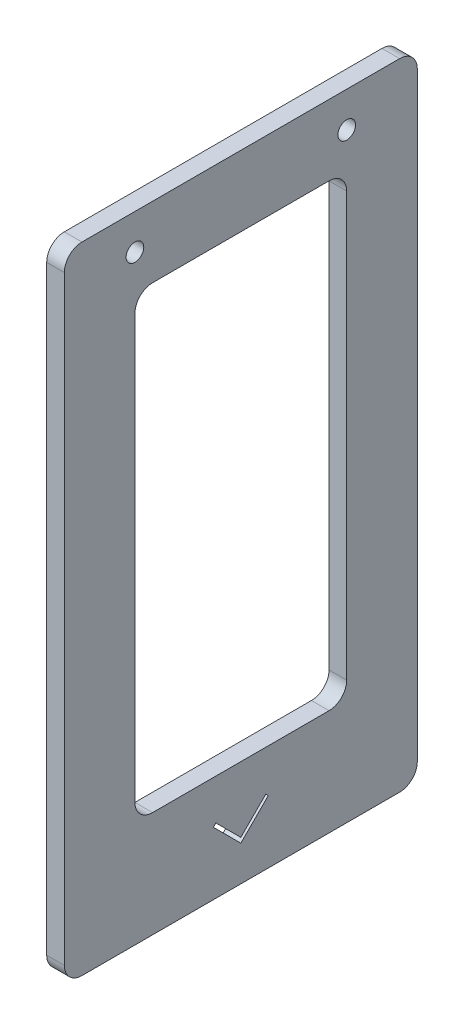
SolidWorks part; units mm, degrees
material "Balsa"
ref_plane "Front Plane" through (0, 0, 0) normal (0, 0, 1) x (1, 0, 0)
ref_plane "Top Plane" through (0, 0, 0) normal (0, 1, 0) x (1, 0, 0)
ref_plane "Right Plane" through (0, 0, 0) normal (1, 0, 0) x (0, 0, -1)
sketch "Sketch3" plane through (0, 0, 0) normal (1, 0, 0) x (0, 0, -1)
  line L0 (-31.75, -76.2) -> (31.75, -76.2)
  line L1 (-57.15, -114.3) -> (57.15, -114.3)
  line L2 (-63.5, -107.95) -> (-63.5, 107.95)
  line L3 (-57.15, 114.3) -> (57.15, 114.3)
  line L4 (63.5, -107.95) -> (63.5, 107.95)
  line L5 (-63.5, -114.3) -> (63.5, 114.3) construction
  line L6 (-63.5, 114.3) -> (63.5, -114.3) construction
  line L8 (-38.1, -69.85) -> (-38.1, 82.55)
  line L9 (-31.75, 88.9) -> (31.75, 88.9)
  line L11 (0, 0) -> (38.1, 88.9) construction
  line L12 (-38.1, 88.9) -> (0, 0) construction
  line L13 (38.1, -69.85) -> (38.1, 82.55)
  arc A0 (-57.15, -114.3) -> (-63.5, -107.95) centre (-57.15, -107.95) cw
  arc A1 (63.5, -107.95) -> (57.15, -114.3) centre (57.15, -107.95) cw
  arc A2 (63.5, 107.95) -> (57.15, 114.3) centre (57.15, 107.95) ccw
  arc A3 (-63.5, 107.95) -> (-57.15, 114.3) centre (-57.15, 107.95) cw
  arc A4 (31.75, -76.2) -> (38.1, -69.85) centre (31.75, -69.85) ccw
  arc A5 (-31.75, -76.2) -> (-38.1, -69.85) centre (-31.75, -69.85) cw
  arc A6 (31.75, 88.9) -> (38.1, 82.55) centre (31.75, 82.55) cw
  arc A7 (-38.1, 82.55) -> (-31.75, 88.9) centre (-31.75, 82.55) cw
  point P0 (0, 0)
  point P6 (0, 0)
  point P26 (38.1, -76.2)
  dimension "D7" = 6.35
  dimension "D8" = 6.35
  dimension "D1" = 228.6
  dimension "D2" = 127
  dimension "D3" = 76.2
  dimension "D4" = 165.1
  dimension "D5" = 25.4
  dimension "D6" = 25.4
extrude "Boss-Extrude2" add sketch "Sketch3" along normal blind 6.35
sketch "Sketch4" plane through (6.35, 0, 0) normal (1, 0, 0) x (0, 0, -1)
  line L5 (0, -99.8039) -> (-8.9803, -90.8237)
  line L6 (-8.9803, -90.8237) -> (-9.8783, -91.7217)
  line L8 (-9.8783, -91.7217) -> (0, -101.6)
  line L9 (0, -101.6) -> (9.8783, -91.7217)
  line L10 (9.8783, -91.7217) -> (8.9803, -90.8237)
  line L11 (8.9803, -90.8237) -> (0, -99.8039)
  line L12 (0, 55) -> (0, -55) construction
  line L13 (-57.15, -114.3) -> (57.15, -114.3) construction
  dimension "D1" = 12.7
  dimension "D2" = 12.7
  dimension "D3" = 1.27
extrude "Cut-Extrude1" cut sketch "Sketch4" against normal up to next
sketch "Sketch5" plane through (6.35, 0, 0) normal (1, 0, 0) x (0, 0, -1)
  line L1 (-63.5, 101.6) -> (-38.1, 101.6) construction
  line L2 (-63.5, 107.95) -> (-63.5, -107.95) construction
  line L3 (-38.1, 101.6) -> (38.1, 101.6) construction
  line L4 (-38.1, 101.6) -> (38.1, 101.6) construction
  line L5 (38.1, 101.6) -> (63.5, 101.6) construction
  line L6 (63.5, -107.95) -> (63.5, 107.95) construction
  line L7 (-108.1488, 88.9) -> (105.3076, 88.9) construction
  line L8 (31.75, 88.9) -> (-31.75, 88.9) construction
  circle A0 centre (-38.1, 101.6) radius 3.175
  circle A1 centre (38.1, 101.6) radius 3.175
  dimension "D3" = 6.35
  dimension "D4" = 6.35
  dimension "D1" = 12.7
  dimension "D2" = 25.4
  dimension "D5" = 25.4
extrude "Cut-Extrude2" cut sketch "Sketch5" against normal through all both and the other way through all
